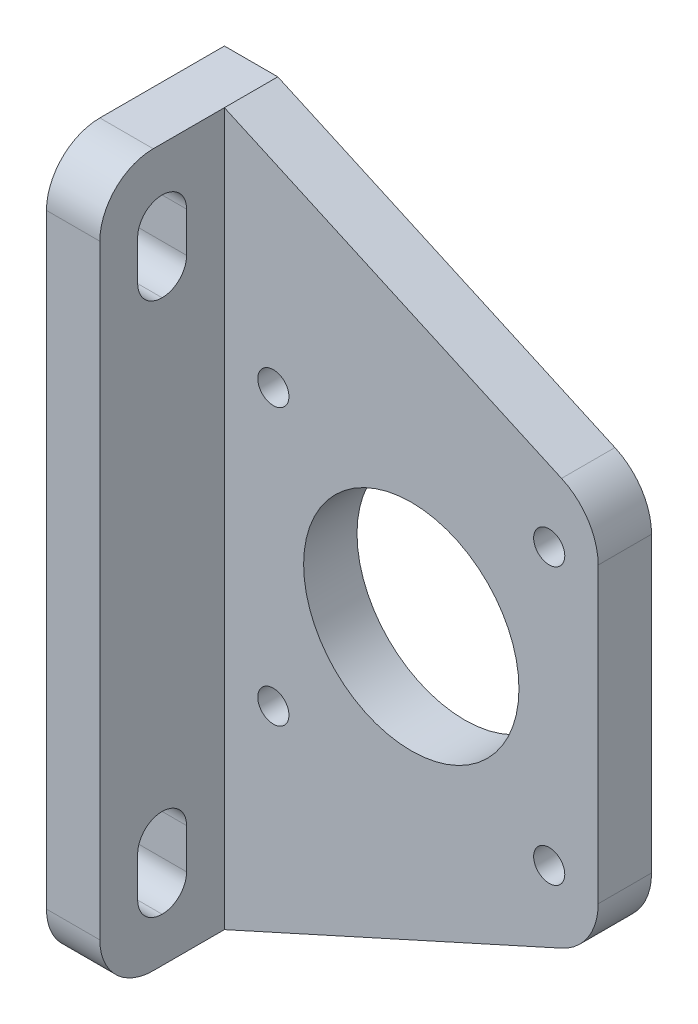
SolidWorks part; units mm, degrees
ref_plane "Front Plane" through (0, 0, 0) normal (0, 0, 1) x (1, 0, 0)
ref_plane "Top Plane" through (0, 0, 0) normal (0, 1, 0) x (1, 0, 0)
ref_plane "Right Plane" through (0, 0, 0) normal (1, 0, 0) x (0, 0, -1)
sketch "Sketch1" plane through (0, 0, 0) normal (0, 0, 1) x (1, 0, 0)
  line L0 (0, 0) -> (-46.4, 0) construction
  line L1 (-21, -21) -> (21, -21) construction
  line L2 (-21, -21) -> (-21, 21) construction
  line L3 (-21, 21) -> (21, 21) construction
  line L4 (21, -21) -> (21, 21)
  line L5 (-21, -21) -> (21, 21) construction
  line L6 (-21, 21) -> (21, -21) construction
  line L7 (-15.5, -15.5) -> (15.5, -15.5) construction
  line L8 (-15.5, -15.5) -> (-15.5, 15.5) construction
  line L9 (-15.5, 15.5) -> (15.5, 15.5) construction
  line L10 (15.5, -15.5) -> (15.5, 15.5) construction
  line L11 (-15.5, -15.5) -> (15.5, 15.5) construction
  line L12 (-15.5, 15.5) -> (15.5, -15.5) construction
  line L13 (-21, 40) -> (-21, -40)
  line L15 (-21, 40) -> (21, 21)
  line L16 (-21, -40) -> (21, -21)
  circle A0 centre (0, 0) radius 12.1
  circle A1 centre (15.5, 15.5) radius 1.75
  circle A2 centre (15.5, -15.5) radius 1.75
  circle A3 centre (-15.5, -15.5) radius 1.75
  circle A4 centre (-15.5, 15.5) radius 1.75
  point P0 (0, 0)
  point P22 (0, 0)
  dimension "D3" = 24.2
  dimension "D6" = 3.5
  dimension "D2" = 42
  dimension "D4" = 31
  dimension "D5" = 31
  dimension "D7" = 4
extrude "Boss-Extrude1" add sketch "Sketch1" along normal blind 6
sketch "Sketch2" plane through (0, 0, 0) normal (0, 0, -1) x (-1, 0, 0)
  circle A0 centre (-15.5, 15.5) radius 3.25
  circle A1 centre (15.5, 15.5) radius 3.25
  circle A2 centre (15.5, -15.5) radius 3.25
  circle A3 centre (-15.5, -15.5) radius 3.25
  point P12 (0, 0)
  dimension "D1" = 6.5
  dimension "D2" = 4
extrude "Cut-Extrude1" cut sketch "Sketch2" against normal blind 3.5
fillet "Fillet2" radius 7 2 edges at (21, 21, 3) (21, -21, 3)
sketch "Sketch4" plane through (0, 0, 0) normal (0, 0, -1) x (-1, 0, 0)
  line L1 (21, 40) -> (27, 40)
  line L2 (21, 40) -> (21, -40)
  line L3 (21, -40) -> (27, -40)
  line L4 (27, 40) -> (27, -40)
  dimension "D1" = 6
extrude "Boss-Extrude2" add sketch "Sketch4" against normal blind 20
sketch "Sketch5" plane through (-21, 0, 0) normal (1, 0, 0) x (0, 0, -1)
  line L0 (-13, 40) -> (-13, -40) construction
  line L1 (-20, 40) -> (-6, 40) construction
  line L2 (-20, -40) -> (-6, -40) construction
  line L3 (0, 0) -> (-13, 0) construction
  line L4 (-15.75, -25) -> (-10.25, -25)
  line L5 (-15.75, -25) -> (-15.75, -35)
  line L6 (-15.75, -35) -> (-10.25, -35)
  line L7 (-10.25, -25) -> (-10.25, -35)
  line L8 (-15.75, -25) -> (-10.25, -35) construction
  line L9 (-15.75, -35) -> (-10.25, -25) construction
  line L10 (-15.75, 35) -> (-10.25, 25) construction
  line L11 (-15.75, 25) -> (-10.25, 35) construction
  line L12 (-10.25, 25) -> (-10.25, 35)
  line L13 (-15.75, 35) -> (-10.25, 35)
  line L14 (-15.75, 25) -> (-15.75, 35)
  line L15 (-15.75, 25) -> (-10.25, 25)
  point P6 (-13, -30)
  point P11 (-15.75, -30)
  point P19 (-13, 30)
  dimension "D1" = 5.5
  dimension "D2" = 10
  dimension "D3" = 10
extrude "Cut-Extrude2" cut sketch "Sketch5" against normal blind 20
fillet "Fillet3" radius 2.75 8 edges at (-24, -25, 15.75) (-24, -25, 10.25) (-24, -35, 15.75) (-24, -35, 10.25) (-24, 35, 15.75) (-24, 25, 15.75) (-24, 25, 10.25) (-24, 35, 10.25)
fillet "Fillet4" radius 6 2 edges at (-24, 40, 20) (-24, -40, 20)
